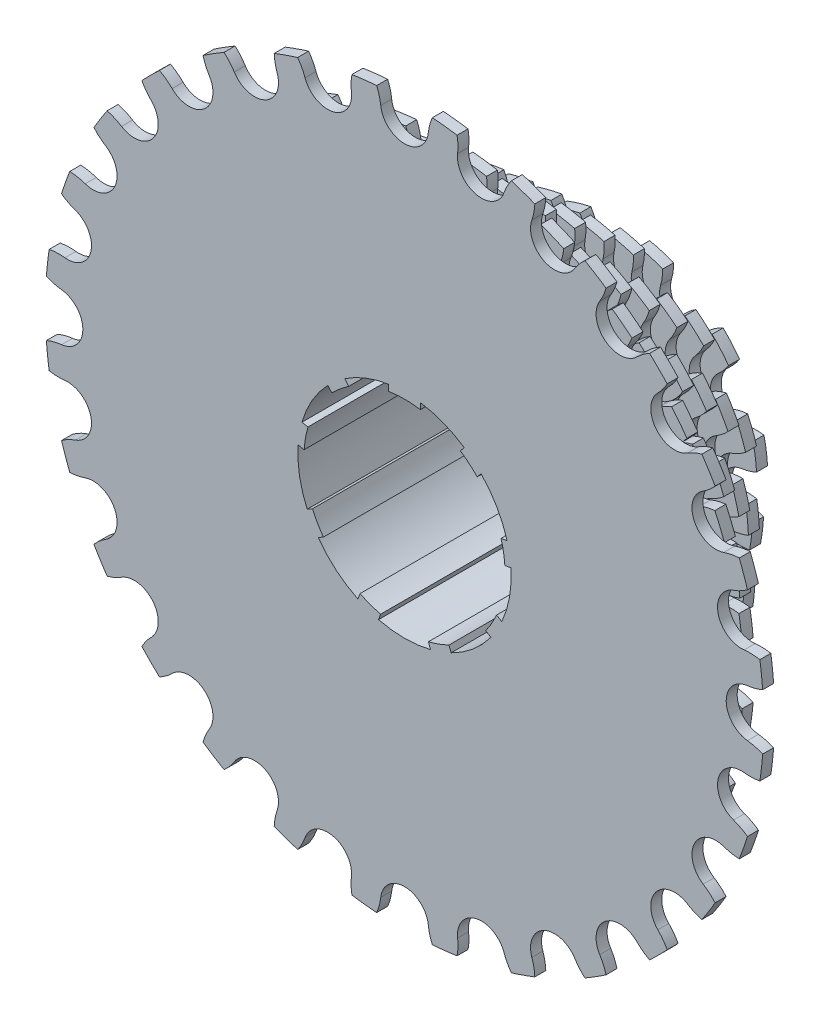
SolidWorks part; units mm, degrees
material "Acero aleado"
ref_plane "Alzado" through (0, 0, 0) normal (0, 0, 1) x (1, 0, 0)
ref_plane "Planta" through (0, 0, 0) normal (0, 1, 0) x (1, 0, 0)
ref_plane "Vista lateral" through (0, 0, 0) normal (1, 0, 0) x (0, 0, -1)
sketch "Sk_Nucleo" plane through (0, 0, 0) normal (0, 0, 1) x (1, 0, 0)
  line L0 (2.6, 17.3058) -> (2.6, 16.2939)
  line L1 (-2.6, 16.2939) -> (-2.6, 17.3058)
  line L2 (-9.8102, 14.4917) -> (-9.1638, 13.7213)
  line L3 (-11.9216, 11.4073) -> (-12.568, 12.1777)
  line L4 (-16.8302, 4.7954) -> (-15.8398, 4.6207)
  line L5 (-16.4649, 1.0754) -> (-17.4553, 1.2501)
  line L6 (-15.9751, -7.1447) -> (-15.1041, -6.6419)
  line L7 (-13.3041, -9.7596) -> (-14.1751, -10.2624)
  line L8 (-7.6451, -15.7418) -> (-7.3011, -14.7968)
  line L9 (-3.9182, -16.028) -> (-4.2622, -16.973)
  line L10 (4.2622, -16.973) -> (3.9182, -16.028)
  line L11 (7.3011, -14.7968) -> (7.6451, -15.7418)
  line L12 (14.1751, -10.2624) -> (13.3041, -9.7596)
  line L13 (15.1041, -6.6419) -> (15.9751, -7.1447)
  line L14 (17.4553, 1.2501) -> (16.4649, 1.0754)
  line L15 (15.8398, 4.6207) -> (16.8302, 4.7954)
  line L16 (12.568, 12.1777) -> (11.9216, 11.4073)
  line L17 (9.1638, 13.7213) -> (9.8102, 14.4917)
  circle A0 centre (0, 0) radius 18.5
  arc A1 (2.6, 16.2939) -> (-2.6, 16.2939) centre (0, 0) ccw
  arc A2 (-2.6, 17.3058) -> (-9.8102, 14.4917) centre (0, 0) ccw
  arc A3 (-9.1638, 13.7213) -> (-11.9216, 11.4073) centre (0, 0) ccw
  arc A4 (-12.568, 12.1777) -> (-16.8302, 4.7954) centre (0, 0) ccw
  arc A5 (-15.8398, 4.6207) -> (-16.4649, 1.0754) centre (0, 0) ccw
  arc A6 (-17.4553, 1.2501) -> (-15.9751, -7.1447) centre (0, 0) ccw
  arc A7 (-15.1041, -6.6419) -> (-13.3041, -9.7596) centre (0, 0) ccw
  arc A8 (-14.1751, -10.2624) -> (-7.6451, -15.7418) centre (0, 0) ccw
  arc A9 (-7.3011, -14.7968) -> (-3.9182, -16.028) centre (0, 0) ccw
  arc A10 (-4.2622, -16.973) -> (4.2622, -16.973) centre (0, 0) ccw
  arc A11 (3.9182, -16.028) -> (7.3011, -14.7968) centre (0, 0) ccw
  arc A12 (7.6451, -15.7418) -> (14.1751, -10.2624) centre (0, 0) ccw
  arc A13 (13.3041, -9.7596) -> (15.1041, -6.6419) centre (0, 0) ccw
  arc A14 (15.9751, -7.1447) -> (17.4553, 1.2501) centre (0, 0) ccw
  arc A15 (16.4649, 1.0754) -> (15.8398, 4.6207) centre (0, 0) ccw
  arc A16 (16.8302, 4.7954) -> (12.568, 12.1777) centre (0, 0) ccw
  arc A17 (11.9216, 11.4073) -> (9.1638, 13.7213) centre (0, 0) ccw
  arc A18 (9.8102, 14.4917) -> (2.6, 17.3058) centre (0, 0) ccw
  dimension "D1" = 37
extrude "Nucleo" add sketch "Sk_Nucleo" along normal blind 35.4
ref_axis "Eje_cassette" through (0, 0, -1.77) along (0, 0, 1)
sketch "Sk_Disco_0" plane through (0, 0, 0) normal (0, 0, 1) x (1, 0, 0)
  circle A0 centre (0, 0) radius 24.2105
  circle A1 centre (0, 0) radius 18.5
  dimension "D1" = 48.4209
  dimension "D2" = 37
extrude "Disco_0" add sketch "Sk_Disco_0" along normal blind 1.8
sketch "Sk_Hueco_0" plane through (0, 0, 0) normal (0, 0, 1) x (1, 0, 0)
  line L0 (0, 0) -> (0, 22.5391) construction
  line L1 (0, 0) -> (-12.1856, 18.9611) construction
  line L2 (0, 0) -> (12.1856, 18.9611) construction
  line L3 (0, 22.5391) -> (-12.1856, 18.9611) construction
  line L4 (0, 22.5391) -> (12.1856, 18.9611) construction
  arc A0 (-3.7686, 21.4326) -> (3.7686, 21.4326) centre (0, 22.5391) ccw
  arc A1 (-3.7686, 21.4326) -> (-6.2793, 25.4472) centre (-12.1856, 18.9611) ccw
  arc A2 (6.2793, 25.4472) -> (3.7686, 21.4326) centre (12.1856, 18.9611) ccw
  arc A3 (6.2793, 25.4472) -> (-6.2793, 25.4472) centre (0, 0) ccw
  dimension "D6" = 3.9277
  dimension "D7" = 26.2105
  dimension "D1" = 22.5391
  dimension "D2" = 22.5391
  dimension "D3" = 22.5391
  dimension "D4" = 32.727
  dimension "D5" = 32.727
extrude "Hueco_0" cut sketch "Sk_Hueco_0" along normal blind 1.8
pattern_circular "Matriz_0" count 11 over 360 about axis through (0, 0, -1.77) along (0, 0, 1) of "Hueco_0"
ref_plane "Plano_1" through (0, 0, 4.8) normal (0, 0, 1) x (1, 0, 0)
sketch "Sk_Disco_1" plane through (0, 0, 4.8) normal (0, 0, 1) x (1, 0, 0)
  circle A0 centre (0, 0) radius 28.3475
  circle A1 centre (0, 0) radius 18.5
  dimension "D2" = 37
  dimension "D1" = 56.6949
extrude "Disco_1" add sketch "Sk_Disco_1" along normal blind 1.8
sketch "Sk_Hueco_1" plane through (0, 0, 4.8) normal (0, 0, 1) x (1, 0, 0)
  line L0 (0, 0) -> (0, 26.534) construction
  line L1 (0, 0) -> (-12.331, 23.4947) construction
  line L2 (0, 0) -> (12.331, 23.4947) construction
  line L3 (0, 26.534) -> (-12.331, 23.4947) construction
  line L4 (0, 26.534) -> (12.331, 23.4947) construction
  arc A0 (-3.8135, 25.594) -> (3.8135, 25.594) centre (0, 26.534) ccw
  arc A1 (-3.8135, 25.594) -> (-6.1485, 29.7181) centre (-12.331, 23.4947) ccw
  arc A2 (6.1485, 29.7181) -> (3.8135, 25.594) centre (12.331, 23.4947) ccw
  arc A3 (6.1485, 29.7181) -> (-6.1485, 29.7181) centre (0, 0) ccw
  dimension "D6" = 3.9277
  dimension "D7" = 30.3475
  dimension "D1" = 26.534
  dimension "D2" = 26.534
  dimension "D3" = 26.534
  dimension "D4" = 27.692
  dimension "D5" = 27.692
extrude "Hueco_1" cut sketch "Sk_Hueco_1" along normal blind 1.8
pattern_circular "Matriz_1" count 13 over 360 about axis through (0, 0, -1.77) along (0, 0, 1) of "Hueco_1"
ref_plane "Plano_2" through (0, 0, 9.6) normal (0, 0, 1) x (1, 0, 0)
sketch "Sk_Disco_2" plane through (0, 0, 9.6) normal (0, 0, 1) x (1, 0, 0)
  circle A0 centre (0, 0) radius 32.4595
  circle A1 centre (0, 0) radius 18.5
  dimension "D2" = 37
  dimension "D1" = 64.919
extrude "Disco_2" add sketch "Sk_Disco_2" along normal blind 1.8
sketch "Sk_Hueco_2" plane through (0, 0, 9.6) normal (0, 0, 1) x (1, 0, 0)
  line L0 (0, 0) -> (0, 30.5418) construction
  line L1 (0, 0) -> (-12.4225, 27.9013) construction
  line L2 (0, 0) -> (12.4225, 27.9013) construction
  line L3 (0, 30.5418) -> (-12.4225, 27.9013) construction
  line L4 (0, 30.5418) -> (12.4225, 27.9013) construction
  arc A0 (-3.8418, 29.7252) -> (3.8418, 29.7252) centre (0, 30.5418) ccw
  arc A1 (-3.8418, 29.7252) -> (-6.0453, 33.9251) centre (-12.4225, 27.9013) ccw
  arc A2 (6.0453, 33.9251) -> (3.8418, 29.7252) centre (12.4225, 27.9013) ccw
  arc A3 (6.0453, 33.9251) -> (-6.0453, 33.9251) centre (0, 0) ccw
  dimension "D6" = 3.9277
  dimension "D7" = 34.4595
  dimension "D1" = 30.5418
  dimension "D2" = 30.5418
  dimension "D3" = 30.5418
  dimension "D4" = 24
  dimension "D5" = 24
extrude "Hueco_2" cut sketch "Sk_Hueco_2" along normal blind 1.8
pattern_circular "Matriz_2" count 15 over 360 about axis through (0, 0, -1.77) along (0, 0, 1) of "Hueco_2"
ref_plane "Plano_3" through (0, 0, 14.4) normal (0, 0, 1) x (1, 0, 0)
sketch "Sk_Disco_3" plane through (0, 0, 14.4) normal (0, 0, 1) x (1, 0, 0)
  circle A0 centre (0, 0) radius 36.5553
  circle A1 centre (0, 0) radius 18.5
  dimension "D2" = 37
  dimension "D1" = 73.1105
extrude "Disco_3" add sketch "Sk_Disco_3" along normal blind 1.8
sketch "Sk_Hueco_3" plane through (0, 0, 14.4) normal (0, 0, 1) x (1, 0, 0)
  line L0 (0, 0) -> (0, 34.5579) construction
  line L1 (0, 0) -> (-12.4838, 32.2243) construction
  line L2 (0, 0) -> (12.4838, 32.2243) construction
  line L3 (0, 34.5579) -> (-12.4838, 32.2243) construction
  line L4 (0, 34.5579) -> (12.4838, 32.2243) construction
  arc A0 (-3.8608, 33.8362) -> (3.8608, 33.8362) centre (0, 34.5579) ccw
  arc A1 (-3.8608, 33.8362) -> (-5.9623, 38.0915) centre (-12.4838, 32.2243) ccw
  arc A2 (5.9623, 38.0915) -> (3.8608, 33.8362) centre (12.4838, 32.2243) ccw
  arc A3 (5.9623, 38.0915) -> (-5.9623, 38.0915) centre (0, 0) ccw
  dimension "D6" = 3.9277
  dimension "D7" = 38.5553
  dimension "D1" = 34.5579
  dimension "D2" = 34.5579
  dimension "D3" = 34.5579
  dimension "D4" = 21.176
  dimension "D5" = 21.176
extrude "Hueco_3" cut sketch "Sk_Hueco_3" along normal blind 1.8
pattern_circular "Matriz_3" count 17 over 360 about axis through (0, 0, -1.77) along (0, 0, 1) of "Hueco_3"
ref_plane "Plano_4" through (0, 0, 19.2) normal (0, 0, 1) x (1, 0, 0)
sketch "Sk_Disco_4" plane through (0, 0, 19.2) normal (0, 0, 1) x (1, 0, 0)
  circle A0 centre (0, 0) radius 40.6399
  circle A1 centre (0, 0) radius 18.5
  dimension "D2" = 37
  dimension "D1" = 81.2798
extrude "Disco_4" add sketch "Sk_Disco_4" along normal blind 1.8
sketch "Sk_Hueco_4" plane through (0, 0, 19.2) normal (0, 0, 1) x (1, 0, 0)
  line L0 (0, 0) -> (0, 38.5796) construction
  line L1 (0, 0) -> (-12.5268, 36.4893) construction
  line L2 (0, 0) -> (12.5268, 36.4893) construction
  line L3 (0, 38.5796) -> (-12.5268, 36.4893) construction
  line L4 (0, 38.5796) -> (12.5268, 36.4893) construction
  arc A0 (-3.8741, 37.9332) -> (3.8741, 37.9332) centre (0, 38.5796) ccw
  arc A1 (-3.8741, 37.9332) -> (-5.8942, 42.2306) centre (-12.5268, 36.4893) ccw
  arc A2 (5.8942, 42.2306) -> (3.8741, 37.9332) centre (12.5268, 36.4893) ccw
  arc A3 (5.8942, 42.2306) -> (-5.8942, 42.2306) centre (0, 0) ccw
  dimension "D6" = 3.9277
  dimension "D7" = 42.6399
  dimension "D1" = 38.5796
  dimension "D2" = 38.5796
  dimension "D3" = 38.5796
  dimension "D4" = 18.947
  dimension "D5" = 18.947
extrude "Hueco_4" cut sketch "Sk_Hueco_4" along normal blind 1.8
pattern_circular "Matriz_4" count 19 over 360 about axis through (0, 0, -1.77) along (0, 0, 1) of "Hueco_4"
ref_plane "Plano_5" through (0, 0, 24) normal (0, 0, 1) x (1, 0, 0)
sketch "Sk_Disco_5" plane through (0, 0, 24) normal (0, 0, 1) x (1, 0, 0)
  circle A0 centre (0, 0) radius 44.7166
  circle A1 centre (0, 0) radius 18.5
  dimension "D2" = 37
  dimension "D1" = 89.4331
extrude "Disco_5" add sketch "Sk_Disco_5" along normal blind 1.8
sketch "Sk_Hueco_5" plane through (0, 0, 24) normal (0, 0, 1) x (1, 0, 0)
  line L0 (0, 0) -> (0, 42.6054) construction
  line L1 (0, 0) -> (-12.5582, 40.7125) construction
  line L2 (0, 0) -> (12.5582, 40.7125) construction
  line L3 (0, 42.6054) -> (-12.5582, 40.7125) construction
  line L4 (0, 42.6054) -> (12.5582, 40.7125) construction
  arc A0 (-3.8838, 42.02) -> (3.8838, 42.02) centre (0, 42.6054) ccw
  arc A1 (-3.8838, 42.02) -> (-5.8374, 46.3504) centre (-12.5582, 40.7125) ccw
  arc A2 (5.8374, 46.3504) -> (3.8838, 42.02) centre (12.5582, 40.7125) ccw
  arc A3 (5.8374, 46.3504) -> (-5.8374, 46.3504) centre (0, 0) ccw
  dimension "D6" = 3.9277
  dimension "D7" = 46.7166
  dimension "D1" = 42.6054
  dimension "D2" = 42.6054
  dimension "D3" = 42.6054
  dimension "D4" = 17.143
  dimension "D5" = 17.143
extrude "Hueco_5" cut sketch "Sk_Hueco_5" along normal blind 1.8
pattern_circular "Matriz_5" count 21 over 360 about axis through (0, 0, -1.77) along (0, 0, 1) of "Hueco_5"
ref_plane "Plano_6" through (0, 0, 28.8) normal (0, 0, 1) x (1, 0, 0)
sketch "Sk_Disco_6" plane through (0, 0, 28.8) normal (0, 0, 1) x (1, 0, 0)
  circle A0 centre (0, 0) radius 50.8209
  circle A1 centre (0, 0) radius 18.5
  dimension "D2" = 37
  dimension "D1" = 101.6418
extrude "Disco_6" add sketch "Sk_Disco_6" along normal blind 1.8
sketch "Sk_Hueco_6" plane through (0, 0, 28.8) normal (0, 0, 1) x (1, 0, 0)
  line L0 (0, 0) -> (0, 48.6492) construction
  line L1 (0, 0) -> (-12.5913, 46.9916) construction
  line L2 (0, 0) -> (12.5913, 46.9916) construction
  line L3 (0, 48.6492) -> (-12.5913, 46.9916) construction
  line L4 (0, 48.6492) -> (12.5913, 46.9916) construction
  arc A0 (-3.8941, 48.1366) -> (3.8941, 48.1366) centre (0, 48.6492) ccw
  arc A1 (-3.8941, 48.1366) -> (-5.7682, 52.505) centre (-12.5913, 46.9916) ccw
  arc A2 (5.7682, 52.505) -> (3.8941, 48.1366) centre (12.5913, 46.9916) ccw
  arc A3 (5.7682, 52.505) -> (-5.7682, 52.505) centre (0, 0) ccw
  dimension "D6" = 3.9277
  dimension "D7" = 52.8209
  dimension "D1" = 48.6492
  dimension "D2" = 48.6492
  dimension "D3" = 48.6492
  dimension "D4" = 15
  dimension "D5" = 15
extrude "Hueco_6" cut sketch "Sk_Hueco_6" along normal blind 1.8
pattern_circular "Matriz_6" count 24 over 360 about axis through (0, 0, -1.77) along (0, 0, 1) of "Hueco_6"
ref_plane "Plano_7" through (0, 0, 33.6) normal (0, 0, 1) x (1, 0, 0)
sketch "Sk_Disco_7" plane through (0, 0, 33.6) normal (0, 0, 1) x (1, 0, 0)
  circle A0 centre (0, 0) radius 58.9466
  circle A1 centre (0, 0) radius 18.5
  dimension "D2" = 37
  dimension "D1" = 117.8931
extrude "Disco_7" add sketch "Sk_Disco_7" along normal blind 1.8
sketch "Sk_Hueco_7" plane through (0, 0, 33.6) normal (0, 0, 1) x (1, 0, 0)
  line L0 (0, 0) -> (0, 56.7144) construction
  line L1 (0, 0) -> (-12.6201, 55.2925) construction
  line L2 (0, 0) -> (12.6201, 55.2925) construction
  line L3 (0, 56.7144) -> (-12.6201, 55.2925) construction
  line L4 (0, 56.7144) -> (12.6201, 55.2925) construction
  arc A0 (-3.903, 56.2747) -> (3.903, 56.2747) centre (0, 56.7144) ccw
  arc A1 (-3.903, 56.2747) -> (-5.6969, 60.6797) centre (-12.6201, 55.2925) ccw
  arc A2 (5.6969, 60.6797) -> (3.903, 56.2747) centre (12.6201, 55.2925) ccw
  arc A3 (5.6969, 60.6797) -> (-5.6969, 60.6797) centre (0, 0) ccw
  dimension "D6" = 3.9277
  dimension "D7" = 60.9466
  dimension "D1" = 56.7144
  dimension "D2" = 56.7144
  dimension "D3" = 56.7144
  dimension "D4" = 12.857
  dimension "D5" = 12.857
extrude "Hueco_7" cut sketch "Sk_Hueco_7" along normal blind 1.8
pattern_circular "Matriz_7" count 28 over 360 about axis through (0, 0, -1.77) along (0, 0, 1) of "Hueco_7"
equation "\"p\" = 12.7"
equation "\"Dr\" = 7.51"
equation "\"e\" = 1.8"
equation "\"Esp\" = 3.0"
equation "\"Desp\" = 37.0"
equation "\"Paso\" = \"e\" + \"Esp\""
equation "\"ri\" = 0.505 * \"Dr\" + 0.069 * \"Dr\" ^ ( 1 / 3 )"
equation "\"Z0\" = 11"
equation "\"D0\" = \"p\" / sin ( 180 / \"Z0\" )"
equation "\"De0\" = \"D0\" + \"p\" * ( 1 - 1.6 / \"Z0\" ) - \"Dr\""
equation "\"Ang0\" = 360 / \"Z0\""
equation "\"Z1\" = 13"
equation "\"D1\" = \"p\" / sin ( 180 / \"Z1\" )"
equation "\"De1\" = \"D1\" + \"p\" * ( 1 - 1.6 / \"Z1\" ) - \"Dr\""
equation "\"Ang1\" = 360 / \"Z1\""
equation "\"Z2\" = 15"
equation "\"D2\" = \"p\" / sin ( 180 / \"Z2\" )"
equation "\"De2\" = \"D2\" + \"p\" * ( 1 - 1.6 / \"Z2\" ) - \"Dr\""
equation "\"Ang2\" = 360 / \"Z2\""
equation "\"Z3\" = 17"
equation "\"D3\" = \"p\" / sin ( 180 / \"Z3\" )"
equation "\"De3\" = \"D3\" + \"p\" * ( 1 - 1.6 / \"Z3\" ) - \"Dr\""
equation "\"Ang3\" = 360 / \"Z3\""
equation "\"Z4\" = 19"
equation "\"D4\" = \"p\" / sin ( 180 / \"Z4\" )"
equation "\"De4\" = \"D4\" + \"p\" * ( 1 - 1.6 / \"Z4\" ) - \"Dr\""
equation "\"Ang4\" = 360 / \"Z4\""
equation "\"Z5\" = 21"
equation "\"D5\" = \"p\" / sin ( 180 / \"Z5\" )"
equation "\"De5\" = \"D5\" + \"p\" * ( 1 - 1.6 / \"Z5\" ) - \"Dr\""
equation "\"Ang5\" = 360 / \"Z5\""
equation "\"Z6\" = 24"
equation "\"D6\" = \"p\" / sin ( 180 / \"Z6\" )"
equation "\"De6\" = \"D6\" + \"p\" * ( 1 - 1.6 / \"Z6\" ) - \"Dr\""
equation "\"Ang6\" = 360 / \"Z6\""
equation "\"Z7\" = 28"
equation "\"D7\" = \"p\" / sin ( 180 / \"Z7\" )"
equation "\"De7\" = \"D7\" + \"p\" * ( 1 - 1.6 / \"Z7\" ) - \"Dr\""
equation "\"Ang7\" = 360 / \"Z7\""
equation "\"D1@Sk_Nucleo\" = \"Desp\""
equation "\"D1@Nucleo\" = 7 * \"Paso\" + \"e\""
equation "\"D1@Sk_Disco_0\" = \"De0\""
equation "\"D2@Sk_Disco_0\" = \"Desp\""
equation "\"D1@Disco_0\" = \"e\""
equation "\"D1@Sk_Hueco_0\" = \"D0\" / 2"
equation "\"D2@Sk_Hueco_0\" = \"D0\" / 2"
equation "\"D3@Sk_Hueco_0\" = \"D0\" / 2"
equation "\"D4@Sk_Hueco_0\" = \"Ang0\""
equation "\"D5@Sk_Hueco_0\" = \"Ang0\""
equation "\"D6@Sk_Hueco_0\" = \"ri\""
equation "\"D7@Sk_Hueco_0\" = \"De0\" / 2 + 2"
equation "\"D1@Hueco_0\" = \"e\""
equation "\"D1@Matriz_0\" = \"Z0\""
equation "\"D1@Sk_Disco_1\" = \"De1\""
equation "\"D2@Sk_Disco_1\" = \"Desp\""
equation "\"D1@Disco_1\" = \"e\""
equation "\"D1@Sk_Hueco_1\" = \"D1\" / 2"
equation "\"D2@Sk_Hueco_1\" = \"D1\" / 2"
equation "\"D3@Sk_Hueco_1\" = \"D1\" / 2"
equation "\"D4@Sk_Hueco_1\" = \"Ang1\""
equation "\"D5@Sk_Hueco_1\" = \"Ang1\""
equation "\"D6@Sk_Hueco_1\" = \"ri\""
equation "\"D7@Sk_Hueco_1\" = \"De1\" / 2 + 2"
equation "\"D1@Hueco_1\" = \"e\""
equation "\"D1@Matriz_1\" = \"Z1\""
equation "\"D1@Sk_Disco_2\" = \"De2\""
equation "\"D2@Sk_Disco_2\" = \"Desp\""
equation "\"D1@Disco_2\" = \"e\""
equation "\"D1@Sk_Hueco_2\" = \"D2\" / 2"
equation "\"D2@Sk_Hueco_2\" = \"D2\" / 2"
equation "\"D3@Sk_Hueco_2\" = \"D2\" / 2"
equation "\"D4@Sk_Hueco_2\" = \"Ang2\""
equation "\"D5@Sk_Hueco_2\" = \"Ang2\""
equation "\"D6@Sk_Hueco_2\" = \"ri\""
equation "\"D7@Sk_Hueco_2\" = \"De2\" / 2 + 2"
equation "\"D1@Hueco_2\" = \"e\""
equation "\"D1@Matriz_2\" = \"Z2\""
equation "\"D1@Sk_Disco_3\" = \"De3\""
equation "\"D2@Sk_Disco_3\" = \"Desp\""
equation "\"D1@Disco_3\" = \"e\""
equation "\"D1@Sk_Hueco_3\" = \"D3\" / 2"
equation "\"D2@Sk_Hueco_3\" = \"D3\" / 2"
equation "\"D3@Sk_Hueco_3\" = \"D3\" / 2"
equation "\"D4@Sk_Hueco_3\" = \"Ang3\""
equation "\"D5@Sk_Hueco_3\" = \"Ang3\""
equation "\"D6@Sk_Hueco_3\" = \"ri\""
equation "\"D7@Sk_Hueco_3\" = \"De3\" / 2 + 2"
equation "\"D1@Hueco_3\" = \"e\""
equation "\"D1@Matriz_3\" = \"Z3\""
equation "\"D1@Sk_Disco_4\" = \"De4\""
equation "\"D2@Sk_Disco_4\" = \"Desp\""
equation "\"D1@Disco_4\" = \"e\""
equation "\"D1@Sk_Hueco_4\" = \"D4\" / 2"
equation "\"D2@Sk_Hueco_4\" = \"D4\" / 2"
equation "\"D3@Sk_Hueco_4\" = \"D4\" / 2"
equation "\"D4@Sk_Hueco_4\" = \"Ang4\""
equation "\"D5@Sk_Hueco_4\" = \"Ang4\""
equation "\"D6@Sk_Hueco_4\" = \"ri\""
equation "\"D7@Sk_Hueco_4\" = \"De4\" / 2 + 2"
equation "\"D1@Hueco_4\" = \"e\""
equation "\"D1@Matriz_4\" = \"Z4\""
equation "\"D1@Sk_Disco_5\" = \"De5\""
equation "\"D2@Sk_Disco_5\" = \"Desp\""
equation "\"D1@Disco_5\" = \"e\""
equation "\"D1@Sk_Hueco_5\" = \"D5\" / 2"
equation "\"D2@Sk_Hueco_5\" = \"D5\" / 2"
equation "\"D3@Sk_Hueco_5\" = \"D5\" / 2"
equation "\"D4@Sk_Hueco_5\" = \"Ang5\""
equation "\"D5@Sk_Hueco_5\" = \"Ang5\""
equation "\"D6@Sk_Hueco_5\" = \"ri\""
equation "\"D7@Sk_Hueco_5\" = \"De5\" / 2 + 2"
equation "\"D1@Hueco_5\" = \"e\""
equation "\"D1@Matriz_5\" = \"Z5\""
equation "\"D1@Sk_Disco_6\" = \"De6\""
equation "\"D2@Sk_Disco_6\" = \"Desp\""
equation "\"D1@Disco_6\" = \"e\""
equation "\"D1@Sk_Hueco_6\" = \"D6\" / 2"
equation "\"D2@Sk_Hueco_6\" = \"D6\" / 2"
equation "\"D3@Sk_Hueco_6\" = \"D6\" / 2"
equation "\"D4@Sk_Hueco_6\" = \"Ang6\""
equation "\"D5@Sk_Hueco_6\" = \"Ang6\""
equation "\"D6@Sk_Hueco_6\" = \"ri\""
equation "\"D7@Sk_Hueco_6\" = \"De6\" / 2 + 2"
equation "\"D1@Hueco_6\" = \"e\""
equation "\"D1@Matriz_6\" = \"Z6\""
equation "\"D1@Sk_Disco_7\" = \"De7\""
equation "\"D2@Sk_Disco_7\" = \"Desp\""
equation "\"D1@Disco_7\" = \"e\""
equation "\"D1@Sk_Hueco_7\" = \"D7\" / 2"
equation "\"D2@Sk_Hueco_7\" = \"D7\" / 2"
equation "\"D3@Sk_Hueco_7\" = \"D7\" / 2"
equation "\"D4@Sk_Hueco_7\" = \"Ang7\""
equation "\"D5@Sk_Hueco_7\" = \"Ang7\""
equation "\"D6@Sk_Hueco_7\" = \"ri\""
equation "\"D7@Sk_Hueco_7\" = \"De7\" / 2 + 2"
equation "\"D1@Hueco_7\" = \"e\""
equation "\"D1@Matriz_7\" = \"Z7\""
